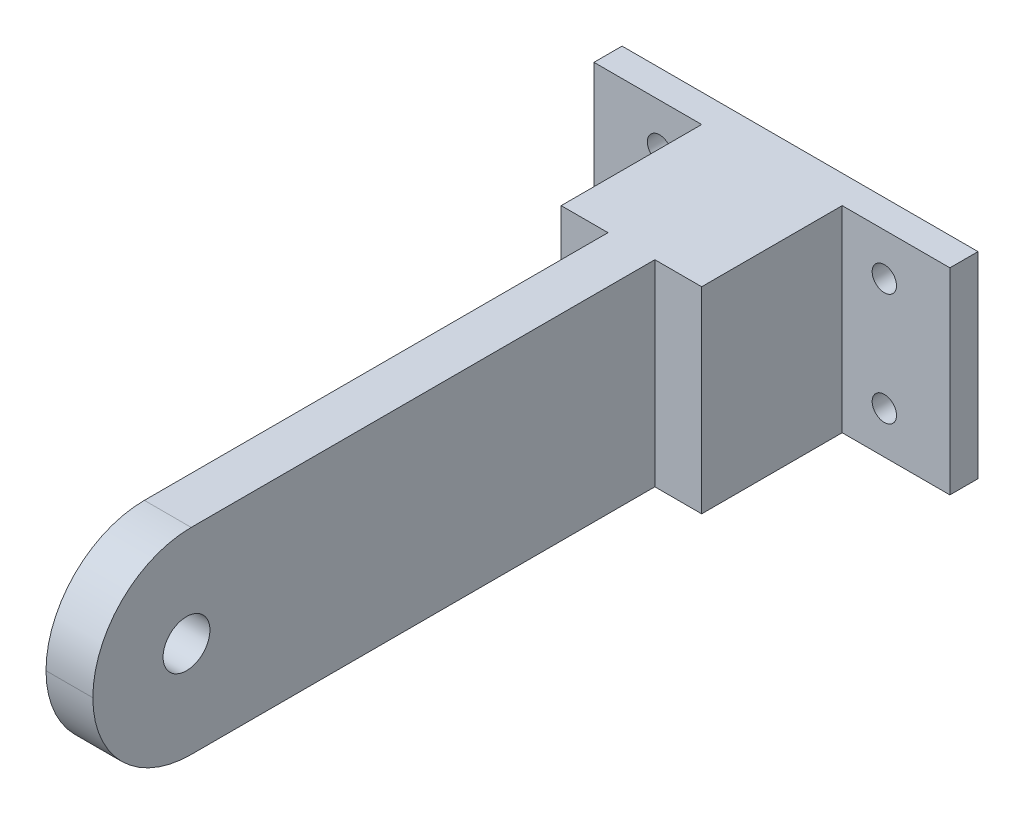
SolidWorks part; units mm, degrees
ref_plane "前视基准面" through (0, 0, 0) normal (0, 0, 1) x (1, 0, 0)
ref_plane "上视基准面" through (0, 0, 0) normal (0, 1, 0) x (1, 0, 0)
ref_plane "右视基准面" through (0, 0, 0) normal (1, 0, 0) x (0, 0, -1)
sketch "草图1" plane through (0, 0, 0) normal (0, 0, 1) x (1, 0, 0)
  line L1 (-27.7897, 8.0949) -> (10.2103, 8.0949)
  line L2 (-27.7897, 8.0949) -> (-27.7897, -12.9051)
  line L3 (-27.7897, -12.9051) -> (10.2103, -12.9051)
  line L4 (10.2103, 8.0949) -> (10.2103, -12.9051)
  dimension "D1" = 38
  dimension "D2" = 21
extrude "凸台-拉伸1" add sketch "草图1" along normal blind 3
sketch "草图2" plane through (0, 0, 3) normal (0, 0, 1) x (1, 0, 0)
  line L0 (10.2103, 8.0949) -> (-27.7897, 8.0949) construction
  line L1 (-27.7897, 8.0949) -> (-27.7897, -12.9051) construction
  line L2 (-27.7897, -12.9051) -> (10.2103, -12.9051) construction
  circle A0 centre (-20.7897, 3.5949) radius 1.3
  circle A1 centre (-20.7897, -8.4051) radius 1.3
  point P10 (0, 0)
  dimension "D1" = 4.5
  dimension "D3" = 4.5
  dimension "D2" = 7
  dimension "D4" = 7
extrude "切除-拉伸1" cut sketch "草图2" against normal blind 3
pattern_linear "阵列(线性)1" count 2 spacing 24 along (1, 0, 0) of "切除-拉伸1"
sketch "草图3" plane through (0, 0, 3) normal (0, 0, 1) x (1, 0, 0)
  line L0 (10.2103, 8.0949) -> (-27.7897, 8.0949) construction
  line L1 (-16.2897, 8.0949) -> (-1.2897, 8.0949)
  line L2 (-16.2897, 8.0949) -> (-16.2897, -12.9051)
  line L3 (-16.2897, -12.9051) -> (-1.2897, -12.9051)
  line L4 (-1.2897, 8.0949) -> (-1.2897, -12.9051)
  line L5 (-27.7897, -12.9051) -> (10.2103, -12.9051) construction
  line L6 (-27.7897, 8.0949) -> (-27.7897, -12.9051) construction
  line L7 (10.2103, -12.9051) -> (10.2103, 8.0949) construction
  dimension "D1" = 11.5
  dimension "D2" = 11.5
extrude "凸台-拉伸2" add sketch "草图3" along normal blind 15
sketch "草图4" plane through (0, 0, 18) normal (0, 0, 1) x (1, 0, 0)
  line L0 (-1.2897, 8.0949) -> (-16.2897, 8.0949) construction
  line L1 (-11.2897, 8.0949) -> (-6.2897, 8.0949)
  line L2 (-11.2897, 8.0949) -> (-11.2897, -12.9051)
  line L3 (-11.2897, -12.9051) -> (-6.2897, -12.9051)
  line L4 (-6.2897, 8.0949) -> (-6.2897, -12.9051)
  line L5 (-16.2897, -12.9051) -> (-1.2897, -12.9051) construction
  line L6 (-16.2897, 8.0949) -> (-16.2897, -12.9051) construction
  line L7 (-1.2897, -12.9051) -> (-1.2897, 8.0949) construction
  dimension "D1" = 5
  dimension "D2" = 5
extrude "凸台-拉伸3" add sketch "草图4" along normal blind 60
sketch "草图5" plane through (-6.2897, 0, 0) normal (1, 0, 0) x (0, 0, -1)
  line L0 (-78, -12.9051) -> (-78, 8.0949) construction
  line L1 (-78, 8.0949) -> (-18, 8.0949) construction
  circle A0 centre (-68, -2.4051) radius 2.5
  dimension "D1" = 10
  dimension "D2" = 10.5
extrude "切除-拉伸2" cut sketch "草图5" against normal blind 60
fillet "圆角1" radius 10.5 2 edges at (-8.7897, 8.0949, 78) (-8.7897, -12.9051, 78)
